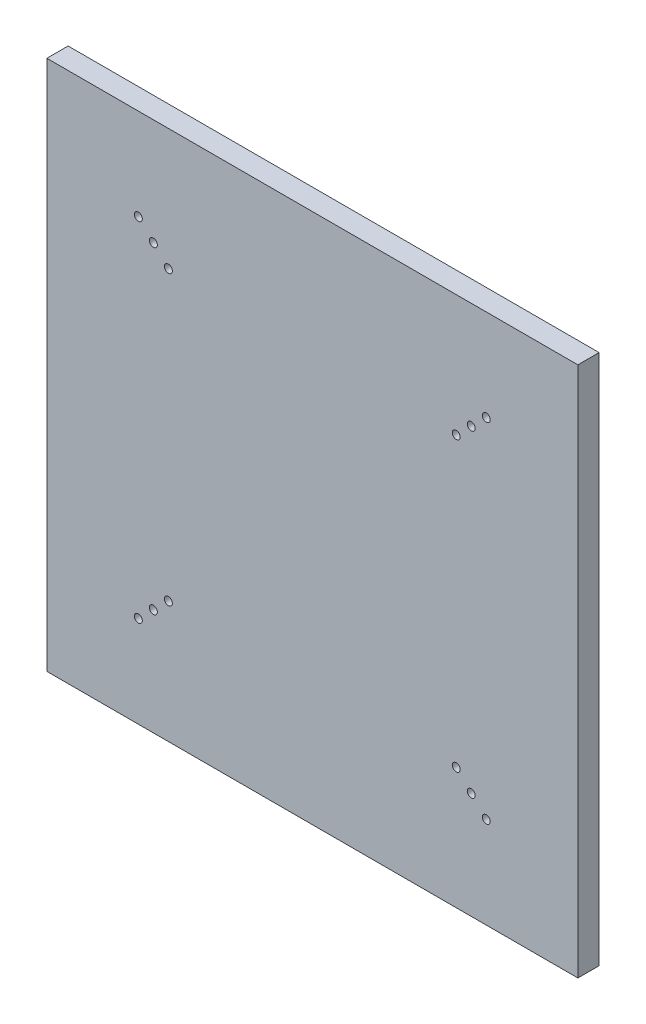
SolidWorks part; units mm, degrees
material "2024-T4"
ref_plane "正面" through (0, 0, 0) normal (0, 0, 1) x (1, 0, 0)
ref_plane "平面" through (0, 0, 0) normal (0, 1, 0) x (1, 0, 0)
ref_plane "右側面" through (0, 0, 0) normal (1, 0, 0) x (0, 0, -1)
sketch "Sketch1" plane through (0, 0, 0) normal (0, 0, 1) x (1, 0, 0)
  line L1 (0, 0) -> (200, 0)
  line L2 (0, 0) -> (0, 200)
  line L3 (0, 200) -> (200, 200)
  line L4 (200, 0) -> (200, 200)
extrude "Boss-Extrude1" add sketch "Sketch1" along normal blind 8
sketch "Sketch2" plane through (0, 0, 8) normal (0, 0, 1) x (1, 0, 0)
  line L0 (0, 200) -> (0, 0) construction
  line L1 (50, 150) -> (150, 150)
  line L2 (50, 150) -> (50, 50)
  line L3 (50, 50) -> (150, 50)
  line L4 (150, 150) -> (150, 50)
  line L5 (200, 0) -> (200, 200) construction
  line L6 (200, 200) -> (0, 200) construction
  line L8 (48, 152) -> (152, 152)
  line L9 (48, 152) -> (48, 48)
  line L10 (48, 48) -> (152, 48)
  line L11 (152, 152) -> (152, 48)
  dimension "D1" = 100
  dimension "D2" = 50
  dimension "D3" = 50
  dimension "D4" = 100
  dimension "D5" = 50
  dimension "D6" = 2
  dimension "D7" = 2
  dimension "D8" = 2
  dimension "D9" = 2
sketch "Sketch3" plane through (0, 0, 8) normal (0, 0, 1) x (1, 0, 0)
  circle A3 centre (165.4957, 34.5043) radius 1.5
  circle A4 centre (159.8388, 40.1612) radius 1.5
  circle A5 centre (154.182, 45.818) radius 1.5
  dimension "D1" = 48.7965
  dimension "D3" = 8
  dimension "D4" = 16
extrude "Cut-Extrude1" cut sketch "Sketch3" against normal blind 4
ref_point "Point1"
ref_axis "Axis1" through (99.9683, 100.0317, 8) along (0, 0, 1)
sketch "Sketch4" plane through (0, 0, 4) normal (0, 0, 1) x (1, 0, 0)
  circle A0 centre (154.182, 45.818) radius 2.5
  circle A1 centre (159.8388, 40.1612) radius 2.5
  circle A2 centre (165.4957, 34.5043) radius 2.5
extrude "Cut-Extrude2" cut sketch "Sketch4" against normal blind 10
pattern_circular "CirPattern1" count 4 over 360 about axis through (99.9683, 100.0317, 8) along (0, 0, 1) of "Cut-Extrude1", "Cut-Extrude2"
